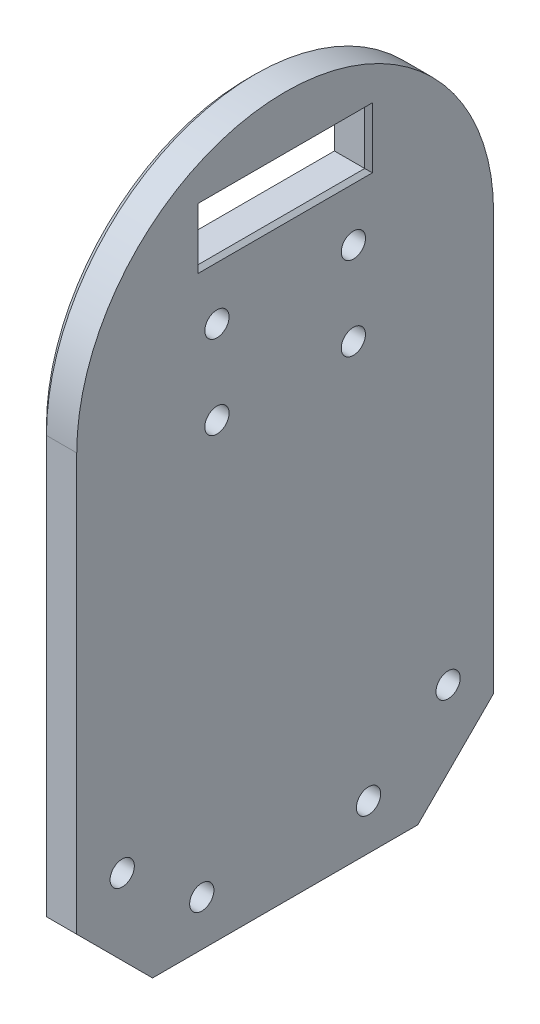
SolidWorks part; units mm, degrees
ref_plane "Front" through (0, 0, 0) normal (0, 0, 1) x (1, 0, 0)
ref_plane "Top" through (0, 0, 0) normal (0, 1, 0) x (1, 0, 0)
ref_plane "Right" through (0, 0, 0) normal (1, 0, 0) x (0, 0, -1)
sketch "草图1" plane through (0, 0, 0) normal (1, 0, 0) x (0, 0, -1)
  line L0 (-27.5, 0) -> (-27.5, -55)
  line L1 (-17.5, -65) -> (17.5, -65)
  line L2 (27.5, -55) -> (27.5, 0)
  line L3 (-27.5, -55) -> (-17.5, -65)
  line L4 (17.5, -65) -> (27.5, -55)
  arc A0 (27.5, 0) -> (-27.5, 0) centre (0, 0) ccw
  circle A1 centre (0, 0) radius 22 construction
  point P5 (-27.5, -65)
  point P6 (27.5, -65)
extrude "凸台-拉伸1" add sketch "草图1" along normal blind 5
sketch "草图2" plane through (5, 0, 0) normal (1, 0, 0) x (0, 0, -1)
  line L1 (-9, -5.5) -> (9, -5.5) construction
  line L2 (-9, -5.5) -> (-9, 5.5) construction
  line L3 (-9, 5.5) -> (9, 5.5) construction
  line L4 (9, -5.5) -> (9, 5.5) construction
  line L5 (-9, -5.5) -> (9, 5.5) construction
  line L6 (-9, 5.5) -> (9, -5.5) construction
  circle A0 centre (-9, 5.5) radius 1.6
  circle A1 centre (9, 5.5) radius 1.6
  circle A2 centre (9, -5.5) radius 1.6
  circle A3 centre (-9, -5.5) radius 1.6
  point P0 (0, 0)
extrude "切除-拉伸1" cut sketch "草图2" against normal blind 5
chamfer "倒角1" distance 1 angle 45 6 edges at (0, -27.5, -27.5) (0, -27.5, 27.5) (0, 27.5, 0) (0, -65, 0) (0, -60, 22.5) (0, -60, -22.5)
sketch "草图3" plane through (5, 0, 0) normal (1, 0, 0) x (0, 0, -1)
  line L0 (27.5, -55) -> (27.5, 0) construction
  line L1 (-17.5, -65) -> (17.5, -65) construction
  line L2 (21.5, -65) -> (21.5, -51) construction
  line L4 (11, -65) -> (11, -59) construction
  circle A0 centre (21.5, -51) radius 1.6
  circle A1 centre (11, -59) radius 1.6
  point P0 (0, 0)
  dimension "D1" = 6
  dimension "D2" = 10.5
sketch "草图4" plane through (0, 0, 0) normal (-1, 0, 0) x (0, 0, 1)
  line L1 (-11, 20) -> (11, 20)
  line L2 (-11, 20) -> (-11, 13)
  line L3 (-11, 13) -> (11, 13)
  line L4 (11, 20) -> (11, 13)
  line L5 (0, 13) -> (0, 20) construction
  line L6 (-11, 16.5) -> (11, 16.5) construction
  circle A0 centre (9, 5.5) radius 1.6 construction
  point P100 (0, 16.5)
  dimension "D1" = 22
  dimension "D2" = 7
  dimension "D3" = 0
  dimension "D4" = 11
extrude "切除-拉伸4" cut sketch "草图4" against normal blind 10
chamfer "倒角2" distance 0.5 angle 45 8 edges at (0, 16.5, 11) (0, 20, 0) (0, 16.5, -11) (0, 13, 0) (5, 16.5, 11) (5, 20, 0) (5, 16.5, -11) (5, 13, 0)
extrude "切除-拉伸5" cut sketch "草图3" against normal blind 10
mirror "镜向1" about plane through (0, 0, 0) normal (0, 0, 1) of "切除-拉伸5"
